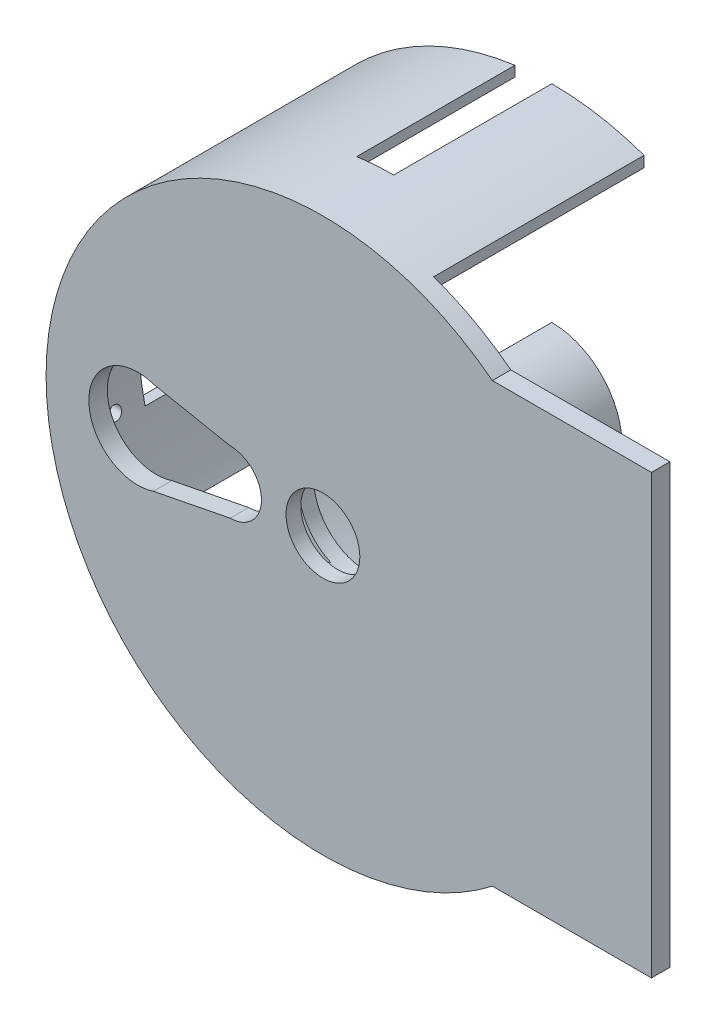
SolidWorks part; units mm, degrees
ref_plane "Front Plane" through (0, 0, 0) normal (0, 0, 1) x (1, 0, 0)
ref_plane "Top Plane" through (0, 0, 0) normal (0, 1, 0) x (1, 0, 0)
ref_plane "Right Plane" through (0, 0, 0) normal (1, 0, 0) x (0, 0, -1)
sketch "Sketch1" plane through (0, 0, 0) normal (0, 0, 1) x (1, 0, 0)
  circle A0 centre (0, 0) radius 75
  dimension "D1" = 150
extrude "Boss-Extrude1" add sketch "Sketch1" along normal blind 52
sketch "Sketch2" plane through (0, 0, 52) normal (0, 0, 1) x (1, 0, 0)
  line L0 (0, 0) -> (-45.9, 0) construction
  line L1 (-45.9, 0) -> (-45.9, 59.3143)
  line L2 (-45.9, 0) -> (-45.9, -59.3143)
  circle A0 centre (0, 0) radius 75 construction
  dimension "D1" = 45.9
ref_point "Point1"
sketch "Sketch5" plane through (0, 0, 0) normal (1, 0, 0) x (0, 0, -1)
  line L0 (-52, 59.3143) -> (-52, 0)
  line L1 (-52, 0) -> (-52, -59.3143) construction
  line L2 (-52, 0) -> (-52, 59.3143) construction
  line L3 (-52, 0) -> (-52, -59.3)
  line L4 (-52, -59.3) -> (-47, -59.3)
  line L5 (-47, -59.3) -> (-47, 59.3143)
  line L6 (-47, 59.3143) -> (-52, 59.3143)
  line L7 (0, 75) -> (-52, 75) construction
  line L8 (-52, -75) -> (0, -75) construction
  dimension "D1" = 5
  dimension "D2" = 15.7
  dimension "D3" = 15.6857
  dimension "D4" = 5
extrude "Boss-Extrude2" add sketch "Sketch5" along normal blind 89
sketch "Sketch6" plane through (0, 0, 0) normal (0, 0, -1) x (-1, 0, 0)
  circle A0 centre (0, 0) radius 67.5
  dimension "D1" = 135
extrude "Cut-Extrude1" cut sketch "Sketch6" against normal blind 40
sketch "Sketch7" plane through (0, 0, 40) normal (0, 0, -1) x (-1, 0, 0)
  circle A0 centre (0, 0) radius 10
  dimension "D1" = 20
extrude "Cut-Extrude2" cut sketch "Sketch7" against normal blind 140
sketch "Sketch8" plane through (0, 0, 40) normal (0, 0, -1) x (-1, 0, 0)
  line L2 (0, 14.5) -> (0, 19)
  line L3 (0, -14.5) -> (0, -19)
  arc A3 (0, 14.5) -> (0, -14.5) centre (0, 0) ccw
  arc A4 (0, 19) -> (0, -19) centre (0, 0) ccw
  dimension "D3" = 4.5
  dimension "D4" = 4.5
extrude "Boss-Extrude3" add sketch "Sketch8" along normal blind 50
sketch "Sketch9" plane through (0, 0, 0) normal (0, 0, 1) x (1, 0, 0)
  line L0 (-13.0962, 7.5797) -> (18.4449, 7.5797) construction
  line L1 (-13.0962, 7.5797) -> (-73.7969, 7.5797)
  line L2 (-13.0962, 7.5797) -> (-13.0962, 13.3797)
  line L3 (-13.0962, 13.3797) -> (-73.7969, 13.3797)
  line L4 (-73.7969, 7.5797) -> (-73.7969, 13.3797)
  circle A0 centre (0, 0) radius 75 construction
  dimension "D1" = 5.8
sketch "Sketch27" plane through (0, 0, 52) normal (0, 0, 1) x (1, 0, 0)
  line L0 (0, 0) -> (-88.2541, 0) construction
  line L1 (0, 0) -> (-16.3, 0)
  line L2 (-16.3, 0) -> (-16.3, -8.25)
  line L3 (-16.3, -8.25) -> (-60.8479, -15.9)
  line L4 (-60.8479, -15.9) -> (-60.8479, 0) construction
  line L5 (-16.3, 0) -> (-16.3, 8.3)
  line L6 (-16.3, 8.3) -> (-60.8565, 15.9)
  line L7 (0, 0) -> (-45.9, 0) construction
  arc A0 (-60.8565, 15.9) -> (-60.8479, -15.9) centre (-54.7609, 0.0016) ccw
  circle A1 centre (-50.154, 0) radius 13.2647
  circle A2 centre (-25.1429, 0) radius 8.4849
  dimension "D1" = 16.3
  dimension "D2" = 8.25
  dimension "D3" = 45.2
  dimension "D4" = 15.9
  dimension "D5" = 8.3
  dimension "D6" = 45.2
  dimension "D7" = 15.9
extrude "Cut-Extrude7" cut sketch "Sketch27" against normal blind 32 contours A2 | A1
sketch "Sketch28" plane through (0, 0, 0) normal (1, 0, 0) x (0, 0, -1)
  line L9 (-29.7344, 16) -> (80.6134, 16)
  line L10 (-29.7344, 16) -> (-29.7344, -16)
  line L11 (-29.7344, -16) -> (80.6134, -16)
  line L13 (80.6134, 16) -> (80.6134, -16)
extrude "Cut-Extrude9" cut sketch "Sketch28" against normal blind 112 contours L11 L13 L9 L10
sketch "Sketch29" plane through (0, 0, 40) normal (0, 0, -1) x (-1, 0, 0)
  line L0 (10.2879, 16) -> (10.2879, -16) construction
  line L1 (65.5763, -16) -> (10.2879, -16) construction
  line L2 (65.5763, 16) -> (10.2879, 16) construction
ref_plane "Plane1" through (-75, 0, 0) normal (1, 0, 0) x (0, 0, -1)
sketch "Sketch30" plane through (-75, 0, 0) normal (1, 0, 0) x (0, 0, -1)
  line L0 (-52, 0) -> (-32.7687, 0) construction
  line L1 (-52, 0) -> (-52, -59.3143) construction
  line L2 (-52, 0) -> (-52, 59.3143) construction
  circle A0 centre (-37.4386, -14) radius 1.75
  dimension "D1" = 3.5
  dimension "D2" = 14
extrude "Cut-Extrude10" cut sketch "Sketch30" along normal blind 10
mirror "Mirror1" about plane through (0, 0, 0) normal (0, 1, 0) of "Cut-Extrude10"
sketch "Sketch31" plane through (0, 0, 40) normal (0, 0, -1) x (-1, 0, 0)
  line L5 (31.7214, 41.0468) -> (14.5546, 41.0468)
  line L6 (31.7214, 41.0468) -> (31.7214, -38.5238)
  line L7 (31.7214, -38.5238) -> (14.5546, -38.5238)
  line L8 (14.5546, 41.0468) -> (14.5546, -38.5238)
extrude "Cut-Extrude11" cut sketch "Sketch31" against normal blind 7
sketch "Sketch32" plane through (-14.5546, 0, 0) normal (-1, 0, 0) x (0, 0, 1)
  line L0 (47, 41.0468) -> (40, 41.0468) construction
  line L1 (47, 39.0468) -> (44, 39.0468)
  line L2 (47, 39.0468) -> (47, -36.5238)
  line L3 (47, -36.5238) -> (44, -36.5238)
  line L4 (44, 39.0468) -> (44, -36.5238)
  line L5 (47, -38.5238) -> (40, -38.5238) construction
  line L6 (47, 41.0468) -> (47, -38.5238) construction
  dimension "D1" = 2
  dimension "D2" = 2
  dimension "D3" = 3
extrude "Cut-Extrude12" cut sketch "Sketch32" against normal blind 8.6
sketch "Sketch34" plane through (0, 0, 40) normal (0, 0, -1) x (-1, 0, 0)
  circle A0 centre (0, 0) radius 14.5
extrude "Cut-Extrude13" cut sketch "Sketch34" against normal blind 8
sketch "Sketch35" plane through (0, 0, 0) normal (0, 0, -1) x (-1, 0, 0)
  circle A0 centre (0, 0) radius 67.5
  circle A1 centre (0, 0) radius 75
extrude "Boss-Extrude4" add sketch "Sketch35" along normal blind 10
sketch "Sketch37" plane through (0, 0, -10) normal (0, 0, -1) x (-1, 0, 0)
  circle A0 centre (0, 0) radius 72.25
  circle A1 centre (0, 0) radius 67.5
  dimension "D1" = 144.5
extrude "Cut-Extrude15" cut sketch "Sketch37" against normal blind 50
sketch "Sketch38" plane through (0, 0, 40) normal (0, 0, -1) x (-1, 0, 0)
  line L0 (31.7214, -5.3588) -> (31.7214, -23)
  line L1 (31.7214, -38.5238) -> (31.7214, -5.3588) construction
  line L2 (0, -23) -> (68.4913, -23)
  line L3 (0, 23) -> (68.4913, 23)
  line L4 (31.7214, -5.3588) -> (31.7214, 23.2028)
  line L5 (31.7214, 5.3588) -> (31.7214, 41.0468) construction
  line L6 (31.7214, 23.2028) -> (68.4913, 23)
  line L7 (31.7214, -23) -> (68.4913, -23)
  arc A0 (0, 23) -> (0, -23) centre (0, 0) ccw
  circle A1 centre (0, 0) radius 72.25 construction
  arc A2 (68.4913, -23) -> (68.4913, 23) centre (0, 0) cw
  arc A3 (68.4913, -23) -> (68.4913, 23) centre (0, 0) ccw
extrude "Cut-Extrude16" cut sketch "Sketch38" against normal blind 7 contours A0 L3 A2 L2
sketch "Sketch39" plane through (0, 0, 40) normal (0, 0, -1) x (-1, 0, 0)
  line L0 (68.4913, 23) -> (31.7214, 23)
  line L1 (31.7214, 23) -> (31.7214, -23)
  line L2 (31.7214, -23) -> (68.4913, -23)
  arc A0 (68.4913, 23) -> (68.4913, -23) centre (0, 0) cw
extrude "Cut-Extrude17" cut sketch "Sketch39" against normal blind 7
ref_plane "Plane3" through (0, 75, 0) normal (0, 1, 0) x (1, 0, 0)
sketch "Sketch42" plane through (0, 75, 0) normal (0, 1, 0) x (1, 0, 0)
  line L0 (75, 10) -> (-75, 10) construction
  line L1 (-75, -34.1) -> (-75, 34.1) construction
  line L3 (-75, -32.845) -> (-10, -32.845)
  line L4 (-10, -32.845) -> (0, -32.845)
  line L5 (-10, -32.845) -> (-10, 10)
  line L6 (-10, 10) -> (0, 10)
  line L7 (0, -32.845) -> (0, 10)
  dimension "D1" = 65
  dimension "D2" = 10
extrude "Cut-Extrude19" cut sketch "Sketch42" against normal up to next contours L5 L4 L7 L6
pattern_circular "CirPattern1" count 5 every 45 about axis through (0, 0, 0) along (0, 0, 1) of "Cut-Extrude19"
pattern_circular "CirPattern2" count 3 every 60 about axis through (0, 0, 0) along (0, 0, 1) of "Cut-Extrude19"
sketch "Sketch43" plane through (0, 0, 52) normal (0, 0, 1) x (1, 0, 0)
  line L0 (-45.9, -12.564) -> (-25.1429, -8.4849)
  line L1 (-45.9, 12.564) -> (-25.1429, 8.4849)
  line L3 (-45.9, 0) -> (-45.9, 59.3143) construction
  line L4 (-45.9, 0) -> (-45.9, -59.3143) construction
  line L5 (-45.9, 12.564) -> (-45.9, -12.564)
  line L6 (-25.1429, 8.4849) -> (-25.1429, -8.4849)
  circle A0 centre (-50.154, 0) radius 13.2647 construction
  circle A1 centre (-25.1429, 0) radius 8.4849 construction
  circle A2 centre (-25.1429, 0) radius 8.4849 construction
extrude "Cut-Extrude20" cut sketch "Sketch43" against normal blind 10
sketch "Sketch44" plane through (0, 75, 0) normal (0, 1, 0) x (1, 0, 0)
  line L0 (89, -47) -> (45.9, -47) construction
  line L1 (75, -47) -> (25, -47)
  line L2 (75, -47) -> (75, 10)
  line L3 (75, 10) -> (25, 10)
  line L4 (25, -47) -> (25, 10)
  line L5 (45.4884, 10) -> (0, 10) construction
  line L6 (75, -32.845) -> (75, 10) construction
  dimension "D1" = 0
  dimension "D2" = 50
extrude "Cut-Extrude21" cut sketch "Sketch44" against normal through all
